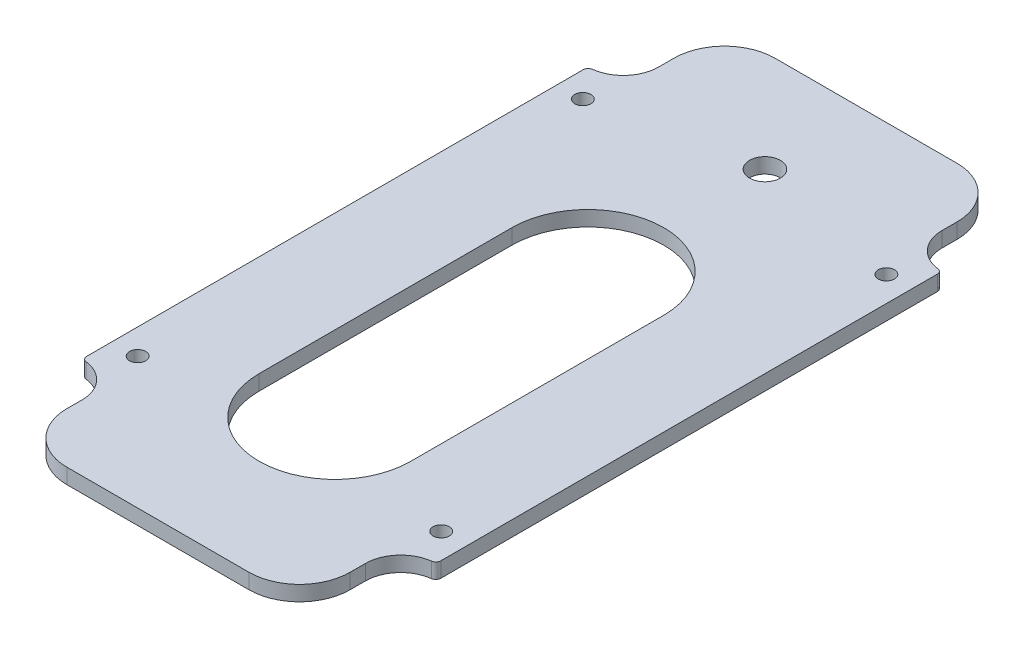
SolidWorks part; units mm, degrees
ref_plane "Front Plane" through (0, 0, 0) normal (0, 0, 1) x (1, 0, 0)
ref_plane "Top Plane" through (0, 0, 0) normal (0, 1, 0) x (1, 0, 0)
ref_plane "Right Plane" through (0, 0, 0) normal (1, 0, 0) x (0, 0, -1)
sketch "Sketch1" plane through (0, 0, 0) normal (0, 1, 0) x (1, 0, 0)
  line L0 (0, 50) -> (0, 132) construction
  line L1 (-35, -50) -> (-28, -50)
  line L2 (-35, -50) -> (-35, 50)
  line L3 (-35, 50) -> (-28, 50)
  line L4 (35, -50) -> (35, 50)
  line L5 (-35, -50) -> (35, 50) construction
  line L6 (-35, 50) -> (35, -50) construction
  line L7 (-30, -44) -> (30, -44) construction
  line L8 (-30, -44) -> (-30, 44) construction
  line L9 (-30, 44) -> (30, 44) construction
  line L10 (30, -44) -> (30, 44) construction
  line L11 (-30, -44) -> (30, 44) construction
  line L12 (-30, 44) -> (30, -44) construction
  line L13 (-28, 132) -> (28, 132) construction
  line L14 (0, 0) -> (-35, 0) construction
  line L15 (-28, 132) -> (-28, 50)
  line L16 (28, 132) -> (28, 50)
  line L17 (28, -132) -> (28, -50)
  line L18 (-28, -132) -> (28, -132) construction
  line L19 (-28, -132) -> (-28, -50)
  line L20 (-28, -50) -> (28, -50) construction
  line L21 (28, -50) -> (35, -50)
  line L22 (0, 50) -> (28, 50) construction
  line L23 (28, 50) -> (35, 50)
  line L24 (-28, 50) -> (0, 50) construction
  line L25 (28, 132) -> (0, 144)
  line L26 (0, 144) -> (-28, 132)
  line L27 (0, -144) -> (-28, -132)
  line L28 (28, -132) -> (0, -144)
  circle A0 centre (-30, 44) radius 1.6
  circle A1 centre (30, 44) radius 1.6
  circle A2 centre (30, -44) radius 1.6
  circle A3 centre (-30, -44) radius 1.6
  point P0 (0, 0)
  point P6 (0, 0)
  point P20 (0, 132)
  dimension "D3" = 3.2
  dimension "D1" = 70
  dimension "D2" = 100
  dimension "D4" = 6
  dimension "D5" = 5
  dimension "D6" = 56
  dimension "D7" = 264
  dimension "D8" = 12
extrude "Boss-Extrude1" add sketch "Sketch1" along normal blind 3
fillet "Fillet1" radius 7 4 edges at (-28, 1.5, 50) (28, 1.5, 50) (28, 1.5, -50) (-28, 1.5, -50)
fillet "Fillet2" radius 1 4 edges at (35, 1.5, -50) (35, 1.5, 50) (-35, 1.5, 50) (-35, 1.5, -50)
fillet "Fillet3" radius 50 2 edges at (0, 1.5, 144) (0, 1.5, -144)
sketch "Sketch2" plane through (0, 3, 0) normal (0, 1, 0) x (1, 0, 0)
  line L0 (-28, 132) -> (-28, 57) construction
  line L1 (-28, 70) -> (31.6267, 70)
  line L2 (-28, 70) -> (-28, 164.2608)
  line L3 (-28, 164.2608) -> (31.6267, 164.2608)
  line L4 (31.6267, 70) -> (31.6267, 164.2608)
  dimension "D1" = 70
extrude "Cut-Extrude1" cut sketch "Sketch2" against normal blind 10
mirror "Mirror1" about plane through (0, 0, 0) normal (0, 0, 1) of "Cut-Extrude1"
fillet "Fillet4" radius 10 4 edges at (-28, 1.5, -70) (28, 1.5, -70) (28, 1.5, 70) (-28, 1.5, 70)
sketch "Sketch3" plane through (0, 3, 0) normal (0, 1, 0) x (1, 0, 0)
  line L0 (0, 15) -> (0, -35) construction
  line L1 (15, 15) -> (15, -35)
  line L2 (-15, 15) -> (-15, -35)
  line L3 (0, 0) -> (0, -10) construction
  line L4 (0, 30) -> (0, 70) construction
  line L5 (-18, 70) -> (18, 70) construction
  arc A0 (15, 15) -> (-15, 15) centre (0, 15) ccw
  arc A1 (-15, -35) -> (15, -35) centre (0, -35) ccw
  circle A2 centre (0, 50) radius 3.048
  point P2 (0, -10)
  dimension "D4" = 6.096
  dimension "D1" = 50
  dimension "D2" = 15
  dimension "D3" = 10
extrude "Cut-Extrude2" cut sketch "Sketch3" against normal blind 10
